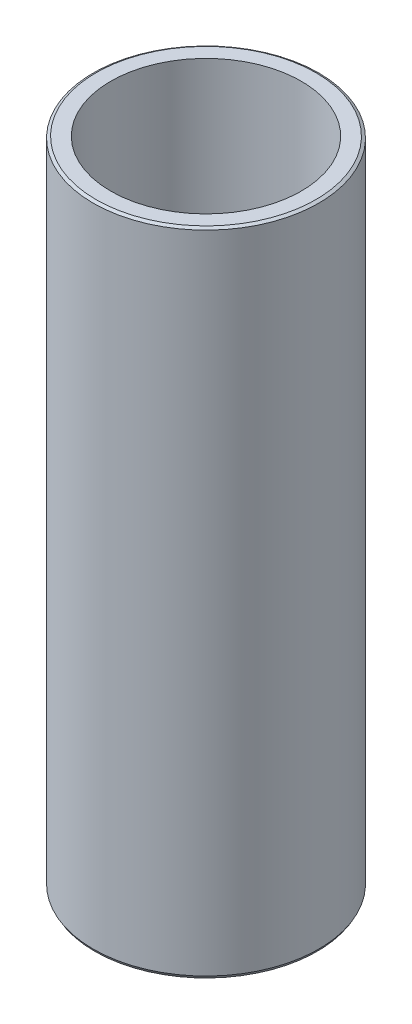
SolidWorks part; units mm, degrees
ref_plane "Front Plane" through (0, 0, 0) normal (0, 0, 1) x (1, 0, 0)
ref_plane "Top Plane" through (0, 0, 0) normal (0, 1, 0) x (1, 0, 0)
ref_plane "Right Plane" through (0, 0, 0) normal (1, 0, 0) x (0, 0, -1)
sketch "Sketch1" plane through (0, 0, 0) normal (0, 1, 0) x (1, 0, 0)
  circle A0 centre (0, 0) radius 37.5
  dimension "SHAFT_OD" = 75
extrude "Boss-Extrude1" add sketch "Sketch1" along normal blind 216.2651
sketch "Sketch2" plane through (0, 0, 0) normal (0, 1, 0) x (1, 0, 0)
  circle A0 centre (0, 0) radius 31.6721
  dimension "BORE_D" = 63.3443
extrude "Cut-Extrude1" cut sketch "Sketch2" along normal through all
chamfer "Chamfer1" distance 0.5477 angle 60 2 edges at (0, 216.2651, 37.5) (0, 0, 37.5) first distance on face at (0, 216.2651, 37.5) first distance on face at (0, 0, 31.6721)
